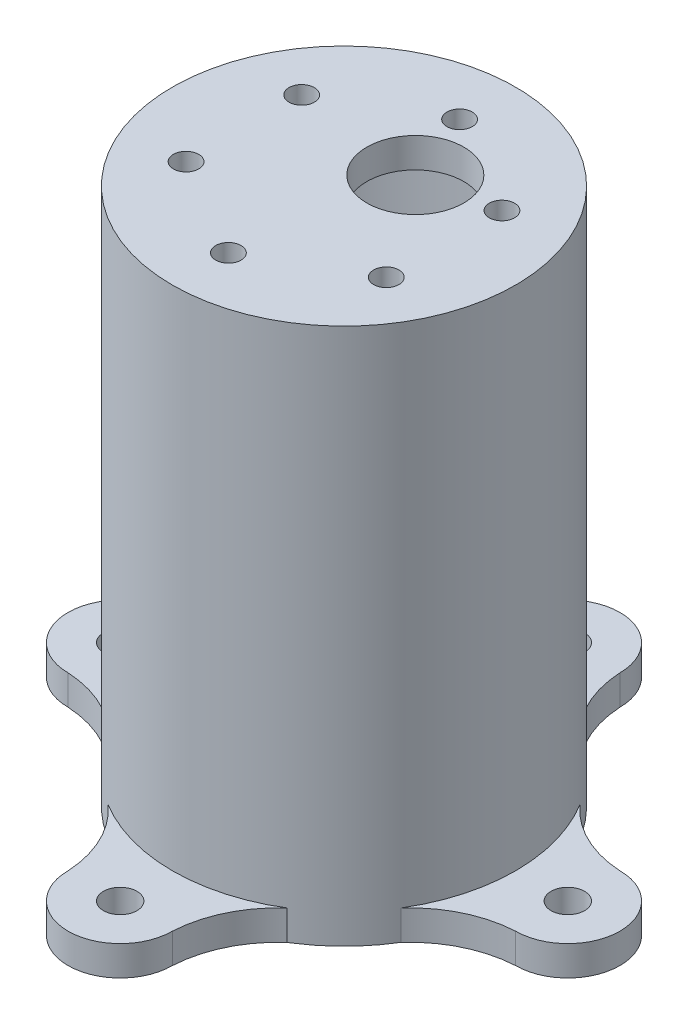
SolidWorks part; units mm, degrees
material "6061-T6 (SS)"
ref_plane "Front Plane" through (0, 0, 0) normal (0, 0, 1) x (1, 0, 0)
ref_plane "Top Plane" through (0, 0, 0) normal (0, 1, 0) x (1, 0, 0)
ref_plane "Right Plane" through (0, 0, 0) normal (1, 0, 0) x (0, 0, -1)
sketch "Sketch2" plane through (0, 0, 0) normal (0, 1, 0) x (1, 0, 0)
  line L0 (0, 37) -> (0, 23) construction
  circle A0 centre (0, 0) radius 19
  circle A1 centre (0, 0) radius 23
  circle A2 centre (0, 0) radius 30 construction
  arc A3 (6.9522, 29.1833) -> (-6.9522, 29.1833) centre (0, 30) ccw
  arc A4 (-7, 30) -> (-12, 19.6214) centre (-21.9775, 30.8219) cw
  arc A5 (7, 30) -> (12, 19.6214) centre (21.9775, 30.8219) ccw
  arc A6 (30, 7) -> (19.6214, 12) centre (30.8219, 21.9775) cw
  arc A7 (29.1833, -6.9522) -> (29.1833, 6.9522) centre (30, 0) ccw
  arc A8 (30, -7) -> (19.6214, -12) centre (30.8219, -21.9775) ccw
  circle A9 centre (0, 0) radius 30 construction
  arc A10 (7, -30) -> (12, -19.6214) centre (21.9775, -30.8219) cw
  arc A11 (-6.9522, -29.1833) -> (6.9522, -29.1833) centre (0, -30) ccw
  arc A12 (-7, -30) -> (-12, -19.6214) centre (-21.9775, -30.8219) ccw
  circle A13 centre (0, 0) radius 30 construction
  arc A14 (-30, -7) -> (-19.6214, -12) centre (-30.8219, -21.9775) cw
  arc A15 (-29.1833, 6.9522) -> (-29.1833, -6.9522) centre (-30, 0) ccw
  arc A16 (-30, 7) -> (-19.6214, 12) centre (-30.8219, 21.9775) ccw
  circle A17 centre (0, 0) radius 30 construction
  circle A18 centre (-30, 0) radius 2.25
  circle A19 centre (0, 30) radius 2.25
  circle A20 centre (0, 0) radius 30 construction
  circle A21 centre (30, 0) radius 2.25
  circle A22 centre (0, 0) radius 30 construction
  circle A23 centre (0, -30) radius 2.25
  circle A24 centre (0, 0) radius 30 construction
  point P46 (0, 0)
  point P60 (0, 0)
  dimension "D1" = 38
  dimension "D2" = 46
  dimension "D3" = 60
  dimension "D4" = 14
  dimension "D5" = 15
  dimension "D8" = 4.5
  dimension "D6" = 12
  dimension "D7" = 4
  dimension "D9" = 4
extrude "Boss-Extrude_flang" add sketch "Sketch2" along normal blind 4 contours A8 A7 A6 A1 A21 | A12 A11 A10 A1 A23 | A16 A15 A14 A1 A18 | A5 A3 A4 A1 A19 region at (22.4245, 0, -6.3136) region at (0, 0, -23.2963) region at (8.197, 0, 24.183) region at (-23.2963, 0, 0)
extrude "Boss-Extrude_wall" add sketch "Sketch2<3>" along normal blind 68 contours A1 A0 region at (21.5131, 0, 6.057)
sketch "Sketch2<3>" plane through (0, 0, 0) normal (0, 1, 0) x (1, 0, 0) same geometry as "Sketch2"
sketch "Sketch5" plane through (0, 68, 0) normal (0, 1, 0) x (1, 0, 0)
  circle A0 centre (0, 0) radius 23
  circle A2 centre (3.5, 6.0622) radius 6.5
  dimension "D1" = 46
  dimension "D2" = 13
extrude "Boss-Extrude4" add sketch "Sketch5" along normal blind 4
sketch "Sketch6" plane through (0, 72, 0) normal (0, 1, 0) x (1, 0, 0)
  circle A0 centre (0, 0) radius 15.5 construction
  circle A1 centre (0, 15.5) radius 1.7
  circle A2 centre (13.4234, 7.75) radius 1.7
  circle A3 centre (0, 0) radius 15.5 construction
  circle A4 centre (13.4234, -7.75) radius 1.7
  circle A5 centre (0, 0) radius 15.5 construction
  circle A6 centre (0, -15.5) radius 1.7
  circle A7 centre (0, 0) radius 15.5 construction
  circle A8 centre (-13.4234, -7.75) radius 1.7
  circle A9 centre (0, 0) radius 15.5 construction
  circle A10 centre (-13.4234, 7.75) radius 1.7
  circle A11 centre (0, 0) radius 15.5 construction
  point P23 (0, 0)
  dimension "D1" = 31
  dimension "D2" = 3.4
extrude "Cut-Extrude2" cut sketch "Sketch6" against normal through all
ref_plane "Plane1" through (-3.4597, 0, -22.7383) normal (-0.1504, 0, -0.9886) x (-0.9886, 0, 0.1504)
sketch "Sketch8" plane through (-3.4597, 0, -22.7383) normal (-0.1504, 0, -0.9886) x (-0.9886, 0, 0.1504)
  line L0 (5.9968, 11.15) -> (-9.0032, 11.15) construction
  line L9 (-1.1147, 11.15) -> (-1.8917, 11.15) construction
  line L12 (5.9968, 9.65) -> (-9.0032, 9.65)
  line L13 (5.9968, 12.65) -> (-9.0032, 12.65)
  arc A4 (5.9968, 9.65) -> (5.9968, 12.65) centre (5.9968, 11.15) ccw
  arc A5 (-9.0032, 12.65) -> (-9.0032, 9.65) centre (-9.0032, 11.15) ccw
  point P9 (-1.5032, 11.15)
  dimension "D2" = 15
  dimension "D1" = 1.5
extrude "Cut-Extrude4" cut sketch "Sketch8" against normal blind 8
equation "\"____ GENERATED PART EXPORTS ____\" = 0"
equation "\"SYS_VersionTag\" = 2"
equation "\"MCB_Enabled\" = 1"
equation "\"MCB_IsStructural\" = 1"
equation "\"MCB_IsSeparablePart\" = 1"
equation "\"MCB_Is3DPrintedPreferred\" = 0"
equation "\"MCB_Height\" = 68mm"
equation "\"MCB_WallThk\" = 4mm"
equation "\"MCB_ClearID\" = 38mm"
equation "\"MCB_OD\" = 46mm"
equation "\"MCB_LowerFlangeOD\" = 60mm"
equation "\"MCB_LowerFlangeThk\" = 4mm"
equation "\"MCB_LowerMountCount\" = 4"
equation "\"MCB_LowerMountClearDia\" = 4.5mm"
equation "\"MCB_LowerMountBCD\" = 60mm"
equation "\"MCB_TopRingThk\" = 4mm"
equation "\"MCB_TopCenterClearDia\" = 13mm"
equation "\"MCB_MotorFaceMountCount\" = 6"
equation "\"MCB_MotorFaceMountBCD\" = 31mm"
equation "\"MCB_MotorFaceMountHoleClearDia\" = 3.4mm"
equation "\"MCB_MotorFaceScrewInsertionMax\" = 3mm"
equation "\"D1@Sketch2\"=\"MCB_ClearID\""
equation "\"D2@Sketch2\"=\"MCB_OD\""
equation "\"D3@Sketch2\"=\"MCB_LowerFlangeOD\""
equation "\"D8@Sketch2\"=\"MCB_LowerMountClearDia\""
equation "\"D1@Boss-Extrude_flang\" = \"MCB_LowerFlangeThk\""
equation "\"D1@Boss-Extrude_wall\" = \"MCB_Height\""
equation "\"D1@Sketch5\"=\"MCB_OD\""
equation "\"D2@Sketch5\"=\"MCB_TopCenterClearDia\""
equation "\"D1@Boss-Extrude4\"=\"MCB_TopRingThk\""
equation "\"D1@Sketch6\"=\"MCB_MotorFaceMountBCD\""
equation "\"D2@Sketch6\"=\"MCB_MotorFaceMountHoleClearDia\""
equation "\"D1@Cut-Extrude4\"=\"MCB_WallThk\"*2"
